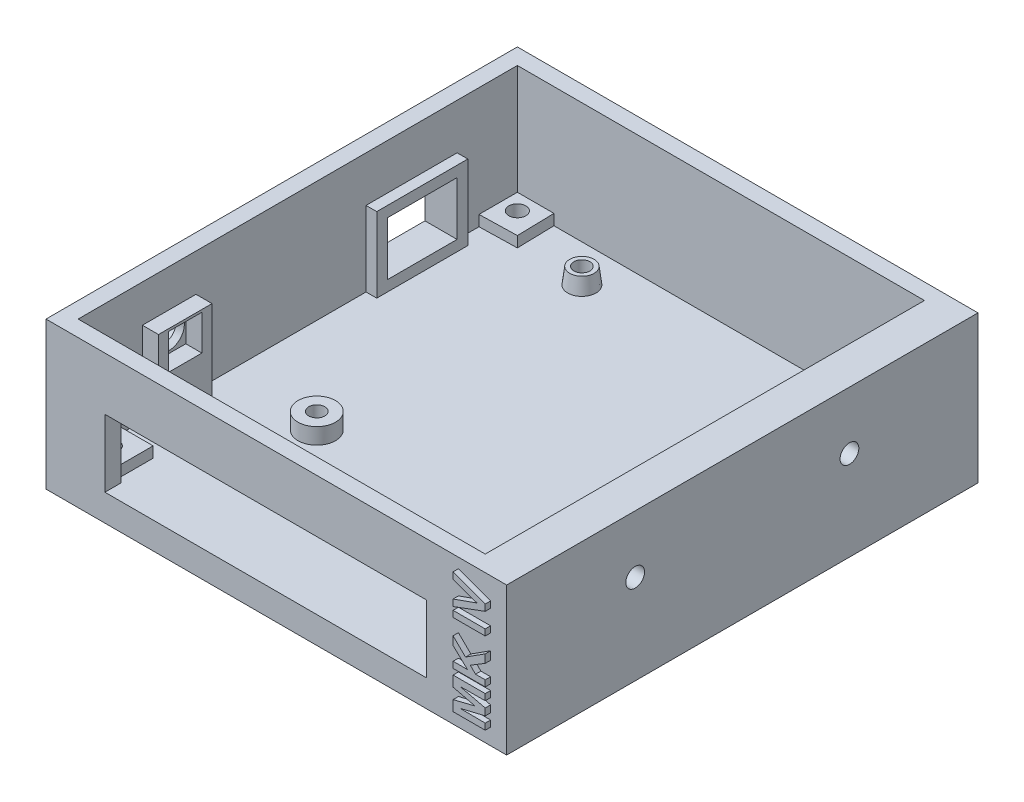
SolidWorks part; units mm, degrees
ref_plane "Спереди" through (0, 0, 0) normal (0, 0, 1) x (1, 0, 0)
ref_plane "Сверху" through (0, 0, 0) normal (0, 1, 0) x (1, 0, 0)
ref_plane "Справа" through (0, 0, 0) normal (1, 0, 0) x (0, 0, -1)
sketch "Sketch1" plane through (0, 0, 0) normal (0, 1, 0) x (1, 0, 0)
  line L1 (41, 44) -> (-41, 44)
  line L2 (41, 44) -> (41, -44)
  line L3 (41, -44) -> (-41, -44)
  line L4 (-41, 44) -> (-41, -44)
  line L5 (41, 44) -> (-41, -44) construction
  line L6 (41, -44) -> (-41, 44) construction
  point P0 (0, 0)
  dimension "D1" = 82
  dimension "D2" = 88
extrude "Boss-Extrude1" add sketch "Sketch1" along normal blind 5
sketch "Sketch2" plane through (0, 5, 0) normal (0, 1, 0) x (1, 0, 0)
  line L1 (-41, 44) -> (41, 44)
  line L2 (-41, 44) -> (-41, -44)
  line L3 (-41, -44) -> (41, -44)
  line L4 (41, 44) -> (41, -44)
  line L5 (-41, 44) -> (41, -44) construction
  line L6 (-41, -44) -> (41, 44) construction
  line L7 (-38, 41) -> (38, 41)
  line L8 (-38, 41) -> (-38, -41)
  line L9 (-38, -41) -> (38, -41)
  line L10 (38, 41) -> (38, -41)
  line L11 (-38, 41) -> (38, -41) construction
  line L12 (-38, -41) -> (38, 41) construction
  point P0 (0, 0)
  point P7 (0, 0)
  dimension "D1" = 3
  dimension "D2" = 3
  dimension "D3" = 76
  dimension "D4" = 82
  dimension "D5" = 82
  dimension "D6" = 88
extrude "Boss-Extrude2" add sketch "Sketch2" along normal blind 22.5
sketch "Эскиз1" plane through (0, 5, 0) normal (0, 1, 0) x (1, 0, 0)
  line L0 (-34.3, 36.65) -> (34.3, 36.65) construction
  line L1 (34.3, -16.65) -> (-34.3, 36.65) construction
  line L2 (-34.3, -16.65) -> (34.3, 36.65) construction
  line L3 (0, 41) -> (0, -41) construction
  line L4 (-38, -41) -> (38, -41) construction
  line L5 (31.8, -14.15) -> (-34.3, -14.15) construction
  line L6 (38, 41) -> (-38, 41) construction
  line L7 (34.3, 36.65) -> (34.3, -16.65) construction
  line L8 (34.3, -16.65) -> (-34.3, -16.65) construction
  line L9 (-34.3, -16.65) -> (-34.3, 36.65) construction
  line L10 (-34.3, 36.65) -> (-20.3, 36.65) construction
  line L11 (31.8, 36.65) -> (31.8, 18.85) construction
  line L12 (31.8, 18.85) -> (31.8, 34.05) construction
  line L13 (-20.3, 36.65) -> (-19, 36.65) construction
  line L14 (-20.3, 36.65) -> (-20.3, -16.65) construction
  line L15 (-19, 36.65) -> (31.8, 36.65) construction
  line L16 (31.8, 36.65) -> (31.8, -16.65) construction
  line L17 (31.8, -16.65) -> (31.8, -14.15) construction
  line L18 (31.8, 34.05) -> (-19, 34.05) construction
  line L19 (-19, 36.65) -> (-19, -16.65) construction
  circle A0 centre (31.8, -9.05) radius 1.5
  circle A1 centre (-20.3, -14.15) radius 1.5
  circle A2 centre (31.8, 18.85) radius 1.5
  circle A3 centre (-19, 34.05) radius 1.5
  circle A4 centre (-20.3, -14.15) radius 3.5
  circle A5 centre (-19, 34.05) radius 3.5
  circle A6 centre (31.8, 18.85) radius 3.5
  circle A7 centre (31.8, -9.05) radius 3.5
  point P3 (0, 10)
  point P11 (-20.3, -14.15)
  point P34 (0, 0)
  dimension "D12" = 3
  dimension "D2" = 7
  dimension "D3" = 53.3
  dimension "D4" = 68.6
  dimension "D5" = 14
  dimension "D6" = 1.3
  dimension "D7" = 50.8
  dimension "D8" = 2.5
  dimension "D9" = 5.1
  dimension "D10" = 27.9
  dimension "D11" = 15.2
  dimension "D13" = 31
extrude "Boss-Extrude3" add sketch "Эскиз1" along normal blind 3
sketch "Sketch4" plane through (-41, 0, 0) normal (-1, 0, 0) x (0, 0, 1)
  line L0 (0, 27.5) -> (0, 0) construction
  line L1 (-27.75, 17) -> (-14.75, 17)
  line L2 (-27.75, 27.5) -> (-27.75, 5) construction
  line L3 (-44, 0) -> (44, 0) construction
  line L4 (-14.75, 5) -> (-14.75, 27.5) construction
  line L5 (26.75, 5) -> (-26.75, 5) construction
  line L6 (-44, 27.5) -> (44, 27.5) construction
  line L7 (-27.75, 17) -> (-27.75, 5)
  line L8 (-27.75, 5) -> (-14.75, 5)
  line L9 (-41, 5) -> (41, 5) construction
  line L10 (-14.75, 5) -> (-14.75, 17)
  line L11 (-44, 27.5) -> (-44, 0) construction
  point P7 (0, 5)
  point P8 (-21.25, 5)
  dimension "D1" = 53.5
  dimension "D2" = 16.25
  dimension "D3" = 13
  dimension "D4" = 12
extrude "Cut-Extrude1" cut sketch "Sketch4" against normal up to surface (3 mm away) up to face at (-38, 16.25, 0)
sketch "Sketch7" plane through (0, 0, 0) normal (0, -1, 0) x (1, 0, 0)
  line L0 (-41, -44) -> (-41, 44) construction
  line L1 (-35, 38) -> (35, -38) construction
  line L2 (35, -38) -> (-35, -38) construction
  line L3 (-35, -38) -> (-35, 38) construction
  line L4 (-35, 38) -> (35, 38) construction
  line L5 (35, 38) -> (35, -38) construction
  line L6 (-41, 44) -> (41, 44) construction
  line L8 (41, 44) -> (41, -44) construction
  line L9 (41, -44) -> (-41, -44) construction
  circle A0 centre (35, -38) radius 1.6
  circle A1 centre (-35, -38) radius 1.6
  circle A2 centre (-35, 38) radius 1.6
  circle A3 centre (35, 38) radius 1.6
  dimension "D2" = 3.2
  dimension "D3" = 6
  dimension "D1" = 6
  dimension "D4" = 6
  dimension "D5" = 6
extrude "Cut-Extrude3" cut sketch "Sketch7" against normal through all
sketch "Sketch8" plane through (0, 0, 0) normal (0, -1, 0) x (1, 0, 0)
  line L0 (-41, 44) -> (41, 44) construction
  line L1 (33.375, 35.1854) -> (36.625, 35.1854)
  line L2 (36.625, 35.1854) -> (38.25, 38)
  line L3 (38.25, 38) -> (36.625, 40.8146)
  line L4 (36.625, 40.8146) -> (33.375, 40.8146)
  line L5 (33.375, 40.8146) -> (31.75, 38)
  line L6 (31.75, 38) -> (33.375, 35.1854)
  line L7 (33.375, -35.1854) -> (31.75, -38)
  line L8 (31.75, -38) -> (33.375, -40.8146)
  line L9 (33.375, -40.8146) -> (36.625, -40.8146)
  line L10 (36.625, -40.8146) -> (38.25, -38)
  line L11 (38.25, -38) -> (36.625, -35.1854)
  line L12 (36.625, -35.1854) -> (33.375, -35.1854)
  line L13 (-36.625, -35.1854) -> (-38.25, -38)
  line L14 (-38.25, -38) -> (-36.625, -40.8146)
  line L15 (-36.625, -40.8146) -> (-33.375, -40.8146)
  line L16 (-33.375, -40.8146) -> (-31.75, -38)
  line L17 (-31.75, -38) -> (-33.375, -35.1854)
  line L18 (-33.375, -35.1854) -> (-36.625, -35.1854)
  line L19 (-36.625, 35.1854) -> (-33.375, 35.1854)
  line L20 (-33.375, 35.1854) -> (-31.75, 38)
  line L21 (-31.75, 38) -> (-33.375, 40.8146)
  line L22 (-33.375, 40.8146) -> (-36.625, 40.8146)
  line L23 (-36.625, 40.8146) -> (-38.25, 38)
  line L24 (-38.25, 38) -> (-36.625, 35.1854)
  line L25 (41, -44) -> (-41, -44) construction
  circle A0 centre (35, 38) radius 3.25 construction
  circle A1 centre (35, -38) radius 3.25 construction
  circle A2 centre (-35, -38) radius 3.25 construction
  circle A3 centre (-35, 38) radius 3.25 construction
  dimension "D1" = 6.5
extrude "Cut-Extrude4" cut sketch "Sketch8" against normal blind 3.5
sketch "Sketch10" plane through (-38, 0, 0) normal (1, 0, 0) x (0, 0, -1)
  line L0 (27.75, 17) -> (14.75, 5) construction
  line L2 (14.75, 5) -> (27.75, 5)
  line L3 (14.75, 5) -> (14.75, 17)
  line L4 (14.75, 17) -> (27.75, 17)
  line L5 (27.75, 5) -> (27.75, 17)
  line L6 (14.75, 5) -> (27.75, 17) construction
  line L7 (14.75, 17) -> (27.75, 5) construction
  line L8 (12.75, 3) -> (29.75, 3)
  line L9 (12.75, 3) -> (12.75, 19)
  line L10 (12.75, 19) -> (29.75, 19)
  line L11 (29.75, 3) -> (29.75, 19)
  line L12 (12.75, 3) -> (29.75, 19) construction
  line L13 (12.75, 19) -> (29.75, 3) construction
  point P4 (21.25, 11)
  point P5 (21.25, 11)
  dimension "D1" = 2
  dimension "D2" = 2
extrude "Boss-Extrude6" add sketch "Sketch10" along normal blind 2
chamfer "Chamfer1" distance 10 angle 7 1 edges at (-19, 8, -30.55) first distance on face at (-19, 8, -30.55)
sketch "Sketch11" plane through (0, 5, 0) normal (0, 1, 0) x (1, 0, 0)
  circle A0 centre (-20.3, -14.15) radius 1.5
  circle A1 centre (-19, 34.05) radius 1.5
  circle A2 centre (31.8, -9.05) radius 1.5
  circle A3 centre (31.8, 18.85) radius 1.5
  circle A4 centre (31.8, 18.85) radius 1.5 construction
extrude "Cut-Extrude5" cut sketch "Sketch11" against normal through all
sketch "Sketch12" plane through (0, 0, 44) normal (0, 0, 1) x (1, 0, 0)
  line L0 (-41, 11.3) -> (41, 11.3) construction
  line L1 (-41, 27.5) -> (-41, 0) construction
  line L2 (41, 27.5) -> (41, 0) construction
  line L3 (-38, 5) -> (38, 5) construction
  line L4 (30, 17.6) -> (-30, 17.6)
  line L5 (30, 17.6) -> (30, 5)
  line L6 (30, 5) -> (-30, 5)
  line L7 (-30, 17.6) -> (-30, 5)
  line L8 (30, 17.6) -> (-30, 5) construction
  line L9 (30, 5) -> (-30, 17.6) construction
  point P6 (0, 11.3)
  dimension "D1" = 12.6
  dimension "D2" = 60
extrude "Cut-Extrude6" cut sketch "Sketch12" against normal up to surface (3 mm away) up to face at (0, 16.25, 41)
sketch "Sketch13" plane through (41, 0, 0) normal (1, 0, 0) x (0, 0, -1)
  line L0 (-44, 16.75) -> (44, 16.75) construction
  line L3 (-44, 27.5) -> (-44, 0) construction
  line L4 (44, 27.5) -> (44, 0) construction
  circle A0 centre (-20, 16.75) radius 1.75
  circle A1 centre (20, 16.75) radius 1.75
  point P10 (0, 16.75)
  point P11 (-44, 13.75)
  dimension "D1" = 40
  dimension "D4" = 3.5
  dimension "D2" = 20
  dimension "D3" = 3
extrude "Cut-Extrude7" cut sketch "Sketch13" against normal up to surface (3 mm away) up to face at (38, 16.25, 0)
sketch "Sketch14" plane through (41, 0, 0) normal (1, 0, 0) x (0, 0, -1)
  line L0 (-44, 13.75) -> (44, 13.75) construction
  line L1 (-44, 27.5) -> (-44, 0) construction
  line L2 (44, 27.5) -> (44, 0) construction
  line L4 (44, 0) -> (-44, 0)
  line L5 (44, 0) -> (44, 27.5)
  line L6 (44, 27.5) -> (-44, 27.5)
  line L7 (-44, 0) -> (-44, 27.5)
  line L8 (44, 0) -> (-44, 27.5) construction
  line L9 (44, 27.5) -> (-44, 0) construction
  circle A0 centre (-20, 16.75) radius 1.75
  circle A1 centre (20, 16.75) radius 1.75
  circle A2 centre (20, 16.75) radius 1.75 construction
  point P6 (0, 13.75)
extrude "Boss-Extrude7" add sketch "Sketch14" along normal blind 4
sketch "Sketch15" plane through (38, 0, 0) normal (-1, 0, 0) x (0, 0, 1)
  circle A0 centre (20, 16.75) radius 3.75
  circle A1 centre (-20, 16.75) radius 3.75
  dimension "D1" = 7.5
extrude "Cut-Extrude8" cut sketch "Sketch15" against normal blind 3
sketch "Sketch16" plane through (-41, 0, 0) normal (-1, 0, 0) x (0, 0, 1)
  line L0 (44, 16.75) -> (-44, 16.75) construction
  line L1 (44, 27.5) -> (44, 0) construction
  line L2 (-44, 27.5) -> (-44, 0) construction
  circle A0 centre (24, 16.75) radius 2.25
  point P6 (44, 13.75)
  dimension "D2" = 4.5
  dimension "D1" = 3
  dimension "D3" = 20
extrude "Cut-Extrude9" cut sketch "Sketch16" against normal up to next
sketch "Sketch17" plane through (-38, 0, 0) normal (1, 0, 0) x (0, 0, -1)
  line L0 (-29, 20.5) -> (-29, 5)
  line L1 (-20.9, 13.45) -> (-27.1, 13.45)
  line L2 (-20.9, 13.45) -> (-20.9, 20.05)
  line L3 (-20.9, 20.05) -> (-27.1, 20.05)
  line L4 (-27.1, 13.45) -> (-27.1, 20.05)
  line L5 (-20.9, 13.45) -> (-27.1, 20.05) construction
  line L6 (-20.9, 20.05) -> (-27.1, 13.45) construction
  line L7 (12.75, 5) -> (-41, 5) construction
  line L8 (-29, 5) -> (-19, 5)
  line L9 (-19, 20.5) -> (-29, 20.5)
  line L10 (-19, 5) -> (-19, 20.5)
  line L11 (-17.8, 12.1) -> (-29, 20.5) construction
  line L12 (-19, 20.5) -> (-29, 13) construction
  point P0 (-24, 16.75)
  point P6 (-24, 16.75)
  dimension "D1" = 6.2
  dimension "D3" = 10
extrude "Boss-Extrude8" add sketch "Sketch17" along normal blind 3
chamfer "Chamfer2" distance 1 angle 30 1 edges at (-38, 16.75, 21.75) first distance on face at (-38, 16.75, 21.75)
sketch "Sketch20" plane through (-41, 0, 0) normal (-1, 0, 0) x (0, 0, 1)
  circle A0 centre (24, 16.75) radius 3
  circle A1 centre (24, 16.75) radius 5
  dimension "D1" = 6
  dimension "D2" = 10
extrude "Boss-Extrude10" add sketch "Sketch20" along normal blind 1
fillet "Fillet3" radius 2 1 edges at (-41, 16.75, 19)
sketch "Sketch21" plane through (0, 5, 0) normal (0, 1, 0) x (1, 0, 0)
  line L0 (-41, 27.75) -> (-36, 27.75)
  line L1 (-36, 27.75) -> (-36, 14.75)
  line L2 (-36, 14.75) -> (-41, 14.75)
  line L3 (-41, 14.75) -> (-41, 27.75)
extrude "Boss-Extrude11" add sketch "Sketch21" along normal blind 2
sketch "Sketch22" plane through (0, 0, 44) normal (0, 0, 1) x (1, 0, 0)
  line L0 (42, 0) -> (42, 27.5) construction
  line L1 (-41, 0) -> (45, 0) construction
  line L2 (-41, 27.5) -> (45, 27.5) construction
  line L3 (45, 27.5) -> (45, 0) construction
  text T0 "<b>MK IV</b>" font "Arial" height 6
  dimension "D1" = 3
extrude "Boss-Extrude12" add sketch "Sketch22" along normal blind 1
sketch "Sketch23" plane through (0, 5, 0) normal (0, 1, 0) x (1, 0, 0)
  line L2 (-31, -41) -> (-31, -34)
  line L3 (-38, -41) -> (-30, -41) construction
  line L4 (-38, -29) -> (-38, -41) construction
  line L5 (-38, -34) -> (-38, -41)
  line L6 (-31, -34) -> (-38, -34)
  line L7 (-31, -41) -> (-38, -41)
  line L8 (31, -41) -> (31, -34)
  line L9 (30, -41) -> (38, -41) construction
  line L10 (31, -34) -> (38, -34)
  line L11 (38, -41) -> (38, 41) construction
  line L12 (38, -34) -> (38, -41)
  line L13 (38, -41) -> (31, -41)
  line L14 (38, 34) -> (31, 34)
  line L15 (31, 34) -> (31, 41)
  line L16 (38, 41) -> (-38, 41) construction
  line L17 (31, 41) -> (38, 41)
  line L18 (38, 41) -> (38, 34)
  line L19 (-38, 41) -> (-38, 29.75) construction
  line L20 (-38, 33.8379) -> (-31.0019, 34.0019)
  line L21 (-31.0019, 34.0019) -> (-31.1659, 41)
  line L22 (-31.1659, 41) -> (-38, 41)
  line L23 (-38, 41) -> (-38, 33.8379)
  circle A4 centre (-35, -38) radius 1.6
  circle A5 centre (-35, 38) radius 1.6
  circle A6 centre (35, 38) radius 1.6
  circle A7 centre (35, -38) radius 1.6
  circle A8 centre (-35, -38) radius 1.6 construction
  dimension "D1" = 7
extrude "Boss-Extrude13" add sketch "Sketch23" along normal blind 2
sketch "Sketch25" plane through (-41, 0, 0) normal (-1, 0, 0) x (0, 0, 1)
  line L0 (-27.75, 12) -> (-14.75, 12) construction
  line L1 (-27.75, 17) -> (-27.75, 7) construction
  line L2 (-14.75, 7) -> (-14.75, 17) construction
  line L4 (-14.75, 7) -> (-27.75, 7)
  line L5 (-14.75, 7) -> (-14.75, 17)
  line L6 (-14.75, 17) -> (-27.75, 17)
  line L7 (-27.75, 7) -> (-27.75, 17)
  line L8 (-14.75, 7) -> (-27.75, 17) construction
  line L9 (-14.75, 17) -> (-27.75, 7) construction
  line L10 (-12.75, 5) -> (-29.75, 5)
  line L11 (-12.75, 5) -> (-12.75, 19)
  line L12 (-12.75, 19) -> (-29.75, 19)
  line L13 (-29.75, 5) -> (-29.75, 19)
  line L14 (-12.75, 5) -> (-29.75, 19) construction
  line L15 (-12.75, 19) -> (-29.75, 5) construction
  point P6 (-21.25, 12)
  point P12 (-21.25, 12)
  dimension "D1" = 2
  dimension "D2" = 2
extrude "Boss-Extrude15" add sketch "Sketch25" along normal up to surface (1 mm away) up to face at (-42, 16.75, 29)
fillet "Fillet4" radius 2 4 edges at (-41, 19, -21.25) (-41, 12, -29.75) (-41, 5, -21.25) (-41, 12, -12.75)
